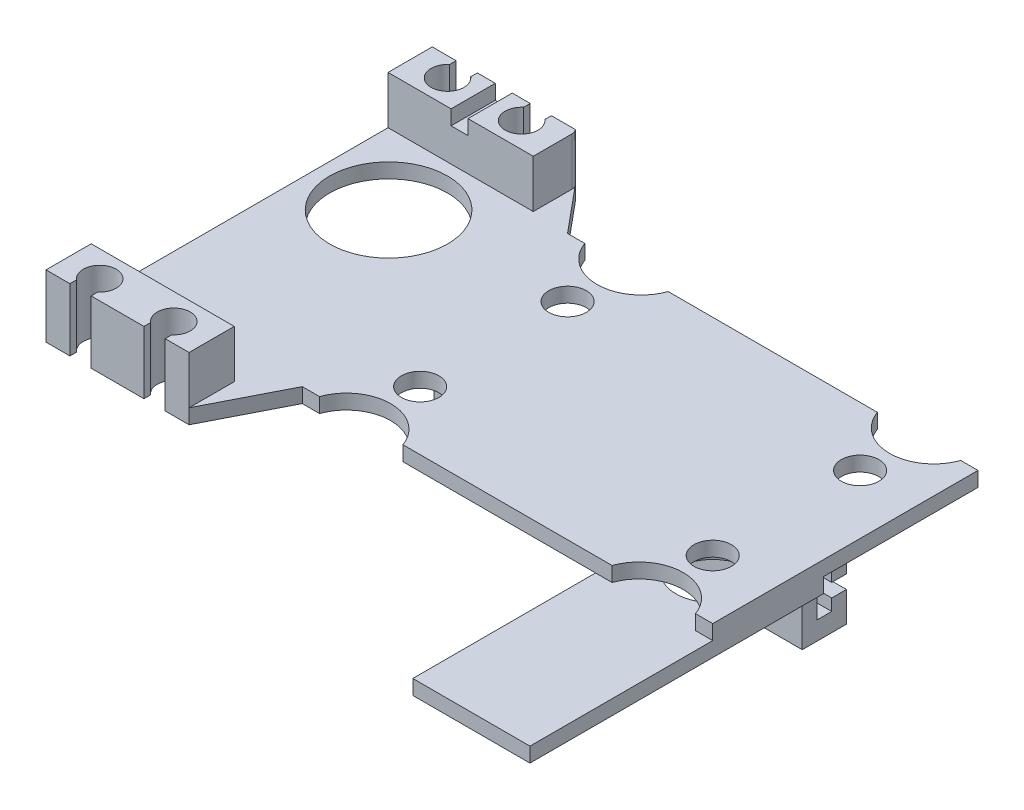
SolidWorks part; units mm, degrees
ref_plane "Front Plane" through (0, 0, 0) normal (0, 0, 1) x (1, 0, 0)
ref_plane "Top Plane" through (0, 0, 0) normal (0, 1, 0) x (1, 0, 0)
ref_plane "Right Plane" through (0, 0, 0) normal (1, 0, 0) x (0, 0, -1)
sketch "Sketch1" plane through (0, 0, 0) normal (1, 0, 0) x (0, 0, -1)
  line L0 (0, 0) -> (6.25, 0)
  line L2 (4, 2.5) -> (2, 2.5)
  line L3 (2, 2.5) -> (2, 7.5)
  line L4 (2, 7.5) -> (4, 7.5)
  line L6 (6.25, 10) -> (0, 10)
  line L7 (0, 10) -> (0, 0)
  line L8 (4, 7.5) -> (4, 5.9125)
  line L9 (4, 5.9125) -> (6, 5.9125)
  line L10 (6, 5.9125) -> (6, 10)
  line L11 (6, 10) -> (6.25, 10)
  line L12 (4, 2.5) -> (4, 4.0875)
  line L13 (4, 4.0875) -> (6, 4.0875)
  line L14 (6, 4.0875) -> (6, 0)
  line L15 (6, 0) -> (6.25, 0)
  dimension "D1" = 5
  dimension "D2" = 1.5875
  dimension "D3" = 2
  dimension "D4" = 2
  dimension "D5" = 2
  dimension "D6" = 10
extrude "Boss-Extrude1" add sketch "Sketch1" along normal blind 50 contours L14 L13 L12 L2 L3 L4 L8 L9 L10 L6 L7 L0 region at (0, 5, -0.1166)
sketch "Sketch2" plane through (0, 10, 0) normal (0, 1, 0) x (1, 0, 0)
  line L1 (-2.85, -15) -> (52.85, -15)
  line L2 (-2.85, -15) -> (-2.85, 21)
  line L3 (-2.85, 21) -> (52.85, 21)
  line L4 (52.85, -15) -> (52.85, 21)
  line L5 (0, 3) -> (50, 3) construction
  line L6 (0, 6) -> (0, 0) construction
  line L7 (50, 6) -> (50, 0) construction
  line L8 (-2.85, 3) -> (52.85, 3) construction
  line L9 (25, 21) -> (25, -15) construction
  line L10 (25, 6) -> (25, 0) construction
  line L11 (50, 6) -> (0, 6) construction
  line L12 (50, 0) -> (0, 0) construction
  line L13 (5.15, -7) -> (44.85, -7) construction
  line L14 (5.15, 13) -> (44.85, 13) construction
  circle A0 centre (5.15, 13) radius 2.55
  circle A1 centre (44.85, 13) radius 2.55
  circle A2 centre (44.85, -7) radius 2.55
  circle A3 centre (5.15, -7) radius 2.55
  dimension "D1" = 5.1
  dimension "D2" = 39.7
  dimension "D3" = 20
  dimension "D4" = 39.7
  dimension "D5" = 8
  dimension "D6" = 8
  dimension "D7" = 8
extrude "Boss-Extrude2" add sketch "Sketch2" along normal blind 2
sketch "Sketch6" plane through (0, 10, 0) normal (0, -1, 0) x (1, 0, 0)
  line L1 (-8.0429, -27.2452) -> (-27.4571, -27.2452)
  line L3 (-8.0429, 25.169) -> (-27.4571, 25.169)
  line L4 (-27.4571, -27.2452) -> (-27.4571, 25.169)
  line L6 (-2.85, -21) -> (-2.85, 15)
  line L9 (-8.0429, -27.2452) -> (-2.85, -21)
  line L10 (-2.85, 15) -> (-8.0429, 25.169)
  arc A0 (-8.75, -27.5381) -> (-7.75, -26.5381) centre (-8.75, -26.5381) ccw construction
  arc A1 (-26.75, 25.4619) -> (-27.75, 24.4619) centre (-26.75, 24.4619) ccw construction
  circle A2 centre (-17.75, -11.6131) radius 8
  point P14 (0, 0)
  dimension "D1" = 16
extrude "Boss-Extrude5" add sketch "Sketch6" against normal blind 2
sketch "Sketch7" plane through (0, 12, 0) normal (0, 1, 0) x (1, 0, 0)
  line L0 (-7.75, 26.5381) -> (-7.75, 20.1131) construction
  line L1 (-27.4571, 27.2452) -> (-7.75, 27.2452)
  line L2 (-27.4571, 27.2452) -> (-27.4571, 21.2452)
  line L3 (-27.4571, 21.2452) -> (-7.75, 21.2452)
  line L4 (-7.75, 27.2452) -> (-7.75, 21.2452)
  line L15 (-27.75, 26.5381) -> (-27.75, 20.1131)
  line L16 (-26.75, 21.1131) -> (-8.75, 21.1131)
  line L17 (-7.75, 20.1131) -> (-7.75, 26.5381)
  line L18 (-8.75, 27.5381) -> (-11.285, 27.5381)
  line L19 (-11.285, 27.5381) -> (-11.285, 26.3473)
  line L20 (-14.165, 26.3473) -> (-14.165, 27.5381)
  line L21 (-14.165, 27.5381) -> (-21.335, 27.5381)
  line L22 (-21.335, 27.5381) -> (-21.335, 26.3473)
  line L23 (-24.215, 26.3473) -> (-24.215, 27.5381)
  line L24 (-24.215, 27.5381) -> (-26.75, 27.5381)
  line L25 (-27.75, 26.5381) -> (-27.75, 20.1131)
  line L26 (-26.75, 21.1131) -> (-8.75, 21.1131)
  line L27 (-7.75, 20.1131) -> (-7.75, 26.5381)
  line L28 (-8.75, 27.5381) -> (-11.285, 27.5381)
  line L29 (-11.285, 27.5381) -> (-11.285, 26.3473)
  line L30 (-14.165, 26.3473) -> (-14.165, 27.5381)
  line L31 (-14.165, 27.5381) -> (-21.335, 27.5381)
  line L32 (-21.335, 27.5381) -> (-21.335, 26.3473)
  line L33 (-24.215, 26.3473) -> (-24.215, 27.5381)
  line L34 (-24.215, 27.5381) -> (-26.75, 27.5381)
  arc A0 (-24.215, 26.3473) -> (-21.335, 26.3473) centre (-22.775, 24.6381) ccw construction
  arc A1 (-24.215, 26.3473) -> (-21.335, 26.3473) centre (-22.775, 24.6381) ccw
  arc A2 (-14.165, 26.3473) -> (-11.285, 26.3473) centre (-12.725, 24.6381) ccw construction
  arc A3 (-14.165, 26.3473) -> (-11.285, 26.3473) centre (-12.725, 24.6381) ccw
  arc A10 (-26.75, 21.1131) -> (-27.75, 20.1131) centre (-26.75, 20.1131) ccw
  arc A11 (-7.75, 20.1131) -> (-8.75, 21.1131) centre (-8.75, 20.1131) ccw
  arc A12 (-7.75, 26.5381) -> (-8.75, 27.5381) centre (-8.75, 26.5381) ccw
  arc A13 (-14.165, 26.3473) -> (-11.285, 26.3473) centre (-12.725, 24.6381) ccw
  arc A14 (-24.215, 26.3473) -> (-21.335, 26.3473) centre (-22.775, 24.6381) ccw
  arc A15 (-26.75, 27.5381) -> (-27.75, 26.5381) centre (-26.75, 26.5381) ccw
  arc A16 (-26.75, 21.1131) -> (-27.75, 20.1131) centre (-26.75, 20.1131) ccw
  arc A17 (-7.75, 20.1131) -> (-8.75, 21.1131) centre (-8.75, 20.1131) ccw
  arc A18 (-7.75, 26.5381) -> (-8.75, 27.5381) centre (-8.75, 26.5381) ccw
  arc A19 (-14.165, 26.3473) -> (-11.285, 26.3473) centre (-12.725, 24.6381) ccw
  arc A20 (-24.215, 26.3473) -> (-21.335, 26.3473) centre (-22.775, 24.6381) ccw
  arc A21 (-26.75, 27.5381) -> (-27.75, 26.5381) centre (-26.75, 26.5381) ccw
  line M22 (-2.85, 21) -> (-8.0429, 27.2452)
  line M23 (-8.0429, 27.2452) -> (-27.4571, 27.2452)
  line M24 (-27.4571, 27.2452) -> (-27.4571, -25.169)
  dimension "D1" = 6
  dimension "D2" = 0
extrude "Boss-Extrude6" add sketch "Sketch7" along normal blind 6.5 contours L4 A18 L29 A3 L30 L32 A1 L33 L3 M22 M23 M24 region at (-17.5508, 12, -23.9953)
sketch "Sketch8" plane through (0, 18.5, 0) normal (0, 1, 0) x (1, 0, 0)
  line L0 (-18.4, 27.5381) -> (-18.4, 21.1131) construction
  line L1 (-17.1, 27.5381) -> (-17.1, 21.1131) construction
  line L2 (-18.4, 27.5381) -> (-18.4, 21.1131) construction
  line L3 (-17.1, 27.5381) -> (-17.1, 21.1131) construction
  line L4 (-18.4, 27.5381) -> (-17.1, 27.5381) construction
  line L5 (-18.4, 21.1131) -> (-17.1, 21.1131) construction
  line L6 (-18.9, 28.0381) -> (-16.6, 28.0381)
  line L7 (-16.6, 28.0381) -> (-16.6, 20.6131)
  line L8 (-18.9, 20.6131) -> (-16.6, 20.6131)
  line L9 (-18.9, 28.0381) -> (-18.9, 20.6131)
  dimension "D1" = 0.5
extrude "Cut-Extrude1" cut sketch "Sketch8" against normal blind 2
sketch "Sketch9" plane through (0, 12, 0) normal (0, 1, 0) x (1, 0, 0)
  line L0 (-18.9, 21.2452) -> (-18.9, 27.2452) construction
  line L1 (-18.9, 27.2452) -> (-21.335, 27.2452) construction
  line L2 (-21.335, 27.2452) -> (-21.335, 26.3473) construction
  line L3 (-24.215, 26.3473) -> (-24.215, 27.2452) construction
  line L4 (-24.215, 27.2452) -> (-27.4571, 27.2452) construction
  line L5 (-27.4571, 27.2452) -> (-27.4571, 21.2452) construction
  line L6 (-27.4571, 21.2452) -> (-18.9, 21.2452) construction
  line L7 (-16.6, 27.2452) -> (-16.6, 21.2452) construction
  line L8 (-16.6, 21.2452) -> (-7.75, 21.2452) construction
  line L9 (-7.75, 21.2452) -> (-7.75, 26.5381) construction
  line L10 (-7.9257, 27.1043) -> (-8.0429, 27.2452) construction
  line L11 (-8.0429, 27.2452) -> (-11.285, 27.2452) construction
  line L12 (-11.285, 27.2452) -> (-11.285, 26.3473) construction
  line L13 (-14.165, 26.3473) -> (-14.165, 27.2452) construction
  line L14 (-14.165, 27.2452) -> (-16.6, 27.2452) construction
  line L15 (-18.9, 21.2452) -> (-18.9, 27.2452)
  line L16 (-18.9, 27.2452) -> (-21.335, 27.2452)
  line L17 (-21.335, 27.2452) -> (-21.335, 26.3473)
  line L18 (-24.215, 26.3473) -> (-24.215, 27.2452)
  line L19 (-24.215, 27.2452) -> (-27.4571, 27.2452)
  line L20 (-27.4571, 27.2452) -> (-27.4571, 21.2452)
  line L21 (-27.4571, 21.2452) -> (-18.9, 21.2452)
  line L22 (-16.6, 27.2452) -> (-16.6, 21.2452)
  line L23 (-16.6, 21.2452) -> (-7.75, 21.2452)
  line L24 (-7.75, 21.2452) -> (-7.75, 26.5381)
  line L25 (-7.9257, 27.1043) -> (-8.0429, 27.2452)
  line L26 (-8.0429, 27.2452) -> (-11.285, 27.2452)
  line L27 (-11.285, 27.2452) -> (-11.285, 26.3473)
  line L28 (-14.165, 26.3473) -> (-14.165, 27.2452)
  line L29 (-14.165, 27.2452) -> (-16.6, 27.2452)
  line L30 (-11.285, 27.2452) -> (-14.165, 27.2452)
  line L31 (-24.215, 27.2452) -> (-21.335, 27.2452)
  line L32 (-14.165, 27.2452) -> (-11.285, 27.2452)
  arc A0 (-24.215, 26.3473) -> (-21.335, 26.3473) centre (-22.775, 24.6381) ccw construction
  arc A1 (-7.75, 26.5381) -> (-7.9257, 27.1043) centre (-8.75, 26.5381) ccw construction
  arc A2 (-14.165, 26.3473) -> (-11.285, 26.3473) centre (-12.725, 24.6381) ccw construction
  arc A3 (-24.215, 26.3473) -> (-21.335, 26.3473) centre (-22.775, 24.6381) ccw
  arc A4 (-7.75, 26.5381) -> (-7.9257, 27.1043) centre (-8.75, 26.5381) ccw
  arc A5 (-14.165, 26.3473) -> (-11.285, 26.3473) centre (-12.725, 24.6381) ccw
  line M1 (-14.165, 27.2452) -> (-14.165, 26.3473)
  arc M2 (-14.165, 26.3473) -> (-11.285, 26.3473) centre (-12.725, 24.6381) ccw
  line M3 (-11.285, 26.3473) -> (-11.285, 27.2452)
  line M4 (-11.285, 27.2452) -> (-14.165, 27.2452)
extrude "Cut-Extrude2" cut sketch "Sketch9" against normal up to surface (2 mm away) contours M4 M1 M2 M3 | L18 A3 L17 L31 region at (-22.775, 12, -24.8463) region at (-12.725, 12, -24.8463) up to face at (25, 10, -3)
sketch "Sketch11" plane through (0, 10, 0) normal (0, -1, 0) x (1, 0, 0)
  line L0 (-14.165, 25.4619) -> (-17.1, 25.4619) construction
  line L2 (-17.1, 19.0369) -> (-8.75, 19.0369) construction
  line L3 (-7.75, 18.0369) -> (-7.75, 24.4619) construction
  line L4 (-8.75, 25.4619) -> (-11.285, 25.4619) construction
  line L5 (-11.285, 25.4619) -> (-11.285, 24.2712) construction
  line L6 (-14.165, 24.2712) -> (-14.165, 25.4619) construction
  line L8 (-18.4, 25.4619) -> (-21.335, 25.4619) construction
  line L9 (-21.335, 25.4619) -> (-21.335, 24.2712) construction
  line L10 (-24.215, 24.2712) -> (-24.215, 25.4619) construction
  line L11 (-24.215, 25.4619) -> (-26.75, 25.4619) construction
  line L12 (-27.75, 24.4619) -> (-27.75, 18.0369) construction
  line L13 (-26.75, 19.0369) -> (-18.4, 19.0369) construction
  line L14 (-14.165, 25.4619) -> (-17.1, 25.4619)
  line L16 (-17.1, 19.0369) -> (-8.75, 19.0369)
  line L17 (-7.75, 18.0369) -> (-7.75, 24.4619)
  line L18 (-8.75, 25.4619) -> (-11.285, 25.4619)
  line L19 (-11.285, 25.4619) -> (-11.285, 24.2712)
  line L20 (-14.165, 24.2712) -> (-14.165, 25.4619)
  line L22 (-18.4, 25.4619) -> (-21.335, 25.4619)
  line L23 (-21.335, 25.4619) -> (-21.335, 24.2712)
  line L24 (-24.215, 24.2712) -> (-24.215, 25.4619)
  line L25 (-24.215, 25.4619) -> (-26.75, 25.4619)
  line L26 (-27.75, 24.4619) -> (-27.75, 18.0369)
  line L27 (-26.75, 19.0369) -> (-18.4, 19.0369)
  line L28 (-17.1, 19.0369) -> (-18.4, 19.0369)
  line L29 (-17.1, 25.4619) -> (-18.4, 25.4619)
  line L30 (-27.4571, 25.169) -> (-27.4571, -27.2452) construction
  line L31 (-8.0429, 25.169) -> (-27.4571, 25.169)
  line L32 (-8.0429, 25.169) -> (-8.0429, 19.0369)
  line L33 (-8.0429, 19.0369) -> (-27.4571, 19.0369)
  line L34 (-27.4571, 25.169) -> (-27.4571, 19.0369)
  arc A0 (-7.75, 18.0369) -> (-8.75, 19.0369) centre (-8.75, 18.0369) ccw construction
  arc A1 (-7.75, 24.4619) -> (-8.75, 25.4619) centre (-8.75, 24.4619) ccw construction
  arc A2 (-14.165, 24.2712) -> (-11.285, 24.2712) centre (-12.725, 22.5619) ccw construction
  arc A3 (-24.215, 24.2712) -> (-21.335, 24.2712) centre (-22.775, 22.5619) ccw construction
  arc A4 (-26.75, 25.4619) -> (-27.75, 24.4619) centre (-26.75, 24.4619) ccw construction
  arc A5 (-26.75, 19.0369) -> (-27.75, 18.0369) centre (-26.75, 18.0369) ccw construction
  arc A6 (-7.75, 18.0369) -> (-8.75, 19.0369) centre (-8.75, 18.0369) ccw
  arc A7 (-7.75, 24.4619) -> (-8.75, 25.4619) centre (-8.75, 24.4619) ccw
  arc A8 (-14.165, 24.2712) -> (-11.285, 24.2712) centre (-12.725, 22.5619) ccw
  arc A9 (-24.215, 24.2712) -> (-21.335, 24.2712) centre (-22.775, 22.5619) ccw
  arc A10 (-26.75, 25.4619) -> (-27.75, 24.4619) centre (-26.75, 24.4619) ccw
  arc A11 (-26.75, 19.0369) -> (-27.75, 18.0369) centre (-26.75, 18.0369) ccw
  line M36 (-8.0429, 25.169) -> (-27.4571, 25.169)
  line M37 (-27.4571, 25.169) -> (-27.4571, -27.2452)
extrude "Boss-Extrude7" add sketch "Sketch11" against normal blind 8.5 contours A9 L24 L33 L27 L28 L16 L32 L19 A8 L20 L23 M36 M37 region at (-17.75, 10, 21.8309)
sketch "Sketch12" plane through (0, 10, 0) normal (0, -1, 0) x (1, 0, 0)
  line L0 (-11.285, 25.169) -> (-14.165, 25.169)
  line L1 (-21.335, 25.169) -> (-24.215, 25.169)
  line L10 (-21.335, 25.169) -> (-21.335, 24.2712)
  line L11 (-14.165, 25.169) -> (-21.335, 25.169)
  line L12 (-14.165, 24.2712) -> (-14.165, 25.169)
  line L13 (-11.285, 25.169) -> (-11.285, 24.2712)
  line L14 (-8.0429, 25.169) -> (-11.285, 25.169)
  line L15 (-8.0429, 19.0369) -> (-8.0429, 25.169)
  line L16 (-27.4571, 19.0369) -> (-8.0429, 19.0369)
  line L17 (-27.4571, 25.169) -> (-27.4571, 19.0369)
  line L18 (-24.215, 25.169) -> (-27.4571, 25.169)
  line L19 (-24.215, 24.2712) -> (-24.215, 25.169)
  line L20 (-21.335, 25.169) -> (-21.335, 24.2712)
  line L21 (-14.165, 25.169) -> (-21.335, 25.169)
  line L22 (-14.165, 24.2712) -> (-14.165, 25.169)
  line L23 (-11.285, 25.169) -> (-11.285, 24.2712)
  line L24 (-8.0429, 25.169) -> (-11.285, 25.169)
  line L25 (-8.0429, 19.0369) -> (-8.0429, 25.169)
  line L26 (-27.4571, 19.0369) -> (-8.0429, 19.0369)
  line L27 (-27.4571, 25.169) -> (-27.4571, 19.0369)
  line L28 (-24.215, 25.169) -> (-27.4571, 25.169)
  line L29 (-24.215, 24.2712) -> (-24.215, 25.169)
  arc A2 (-24.215, 24.2712) -> (-21.335, 24.2712) centre (-22.775, 22.5619) ccw
  arc A3 (-14.165, 24.2712) -> (-11.285, 24.2712) centre (-12.725, 22.5619) ccw
  arc A4 (-24.215, 24.2712) -> (-21.335, 24.2712) centre (-22.775, 22.5619) ccw
  arc A5 (-14.165, 24.2712) -> (-11.285, 24.2712) centre (-12.725, 22.5619) ccw
  line M14 (-8.0429, 25.169) -> (-27.4571, 25.169)
  dimension "D1" = 0
extrude "Cut-Extrude3" cut sketch "Sketch12" against normal up to surface (2 mm away) contours L29 A4 L20 M14 | L22 A5 L23 M14 region at (-12.725, 10, 22.7701) region at (-22.775, 10, 22.7701) up to face at (5.15, 12, -10.45)
sketch "Sketch13" plane through (0, 10, 0) normal (0, -1, 0) x (1, 0, 0)
  line L0 (44.85, -13) -> (44.85, 7) construction
  line L1 (5.15, -13) -> (5.15, 7) construction
  circle A0 centre (44.85, -23) radius 6
  circle A1 centre (44.85, 17) radius 6
  circle A2 centre (5.15, 17) radius 6
  circle A3 centre (5.15, -23) radius 6
  dimension "D2" = 12
  dimension "D1" = 10
  dimension "D3" = 10
  dimension "D4" = 10
  dimension "D5" = 10
extrude "Cut-Extrude4" cut sketch "Sketch13" against normal up to surface (2 mm away) contours A2 | A1 | A0 | A3 up to face at (5.15, 12, -10.45)
sketch "Sketch14" plane through (0, 10, 0) normal (0, -1, 0) x (1, 0, 0)
  line L0 (50, 0) -> (0, 0) construction
  line L1 (36.95, 0) -> (52.85, 0)
  line L2 (36.95, 0) -> (36.95, 39.8)
  line L3 (36.95, 39.8) -> (52.85, 39.8)
  line L4 (52.85, 0) -> (52.85, 39.8)
  line L5 (50, 0) -> (0, 0)
  line L6 (52.85, 15) -> (52.85, -21) construction
  line L7 (52.85, 15) -> (52.85, -21)
  circle A0 centre (44.85, 7) radius 5
  circle A1 centre (44.85, 7) radius 2.55 construction
  circle A2 centre (44.85, 7) radius 2.55
  line M13 (52.85, -21) -> (52.85, 15)
  line M14 (52.85, 15) -> (50.5069, 15)
  arc M15 (50.5069, 15) -> (39.1931, 15) centre (44.85, 17) cw
  line M16 (39.1931, 15) -> (10.8069, 15)
  line M43 (0, 0) -> (50, 0)
  dimension "D3" = 10
  dimension "D1" = 39.8
  dimension "D2" = 15.9
extrude "Boss-Extrude8" add sketch "Sketch14" along normal blind 2 contours A0 L2 L1 M15 M16 M43 M13 M14 | A0 L4 L3 L2 M15 M14 M16 region at (37.1686, 10, 7.5) region at (44.8965, 10, 26.4217)
